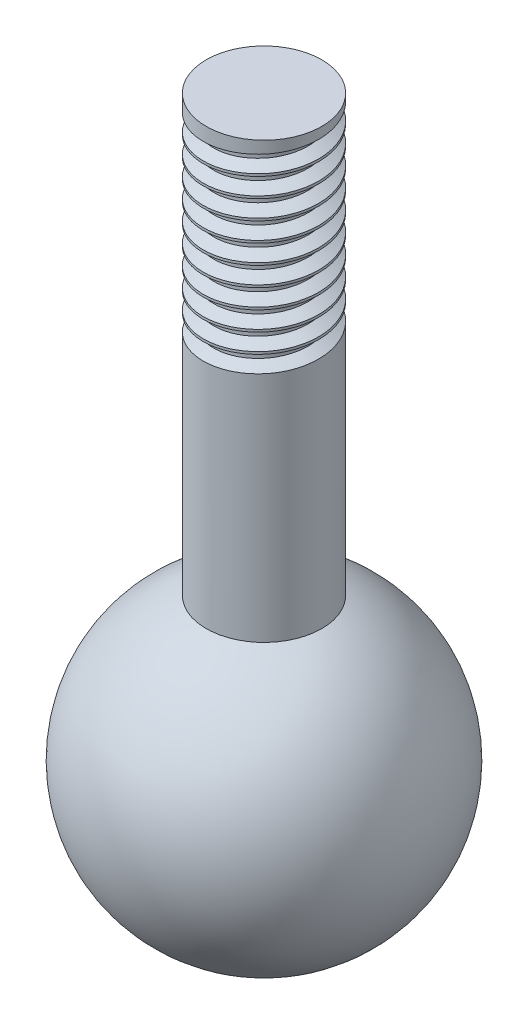
SolidWorks part; units mm, degrees
ref_plane "Front Plane" through (0, 0, 0) normal (0, 0, 1) x (1, 0, 0)
ref_plane "Top Plane" through (0, 0, 0) normal (0, 1, 0) x (1, 0, 0)
ref_plane "Right Plane" through (0, 0, 0) normal (1, 0, 0) x (0, 0, -1)
sketch "Sketch1" plane through (0, 0, 0) normal (0, 0, 1) x (1, 0, 0)
  line L0 (0, 8) -> (0, -8)
  arc A0 (0, 8) -> (0, -8) centre (0, 0) cw
  dimension "D1" = 8
revolve "Revolve1" add sketch "Sketch1" angle 360 about L0
sketch "Sketch2" plane through (0, 0, 0) normal (0, 1, 0) x (1, 0, 0)
  circle A0 centre (0, 0) radius 3
  dimension "D1" = 6
extrude "Boss-Extrude1" add sketch "Sketch2" along normal blind 30
thread "Thread1" pitch 1 method cut profile "Thread Profile1" start angle 0, offset 0, length 10, pitch 1, diameter 6
ref_plane "Plane1" through (-3, 30, 0) normal (0, 0, 1) x (-1, 0, 0)
sketch "Thread Profile1" plane through (-3, 30, 0) normal (0, 0, 1) x (-1, 0, 0)
  line L0 (0, 0) -> (0, 1) construction
  line L11 (0, 0) -> (0, 0.875)
  line L12 (0, 0.875) -> (-0.5413, 0.5625)
  line L13 (-0.5413, 0.5625) -> (-0.5413, 0.3125)
  line L15 (-0.5413, 0.3125) -> (0, 0)
  line L17 (-0.5413, 0.4375) -> (0, 0.4375) construction
  point P2 (0, 0)
  dimension "Pitch" = 1
  dimension "Profile_Angle" = 60
  dimension "Profile_Land" = 0.25
  dimension "Profile_Height" = 0.5413
